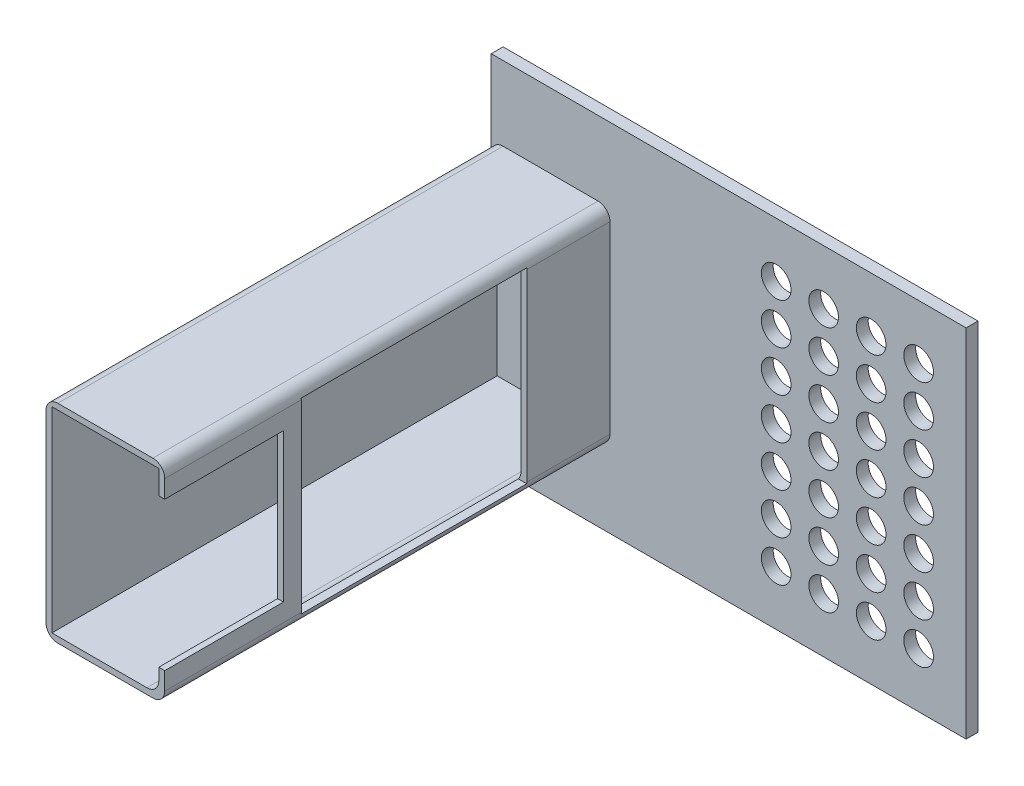
SolidWorks part; units mm, degrees
ref_plane "前视基准面" through (0, 0, 0) normal (0, 0, 1) x (1, 0, 0)
ref_plane "上视基准面" through (0, 0, 0) normal (0, 1, 0) x (1, 0, 0)
ref_plane "右视基准面" through (0, 0, 0) normal (1, 0, 0) x (0, 0, -1)
other "Configuration Table"
sketch "草图1" plane through (0, 0, 0) normal (0, 0, 1) x (1, 0, 0)
  line L1 (0, 0) -> (80, 0)
  line L2 (0, 0) -> (0, -60)
  line L3 (0, -60) -> (80, -60)
  line L4 (80, 0) -> (80, -60)
  dimension "D1" = 80
  dimension "D2" = 60
extrude "凸台-拉伸1" add sketch "草图1" along normal blind 2
sketch "草图3" plane through (0, 0, 2) normal (0, 0, 1) x (1, 0, 0)
  circle A5 centre (48, -50.7846) radius 2.5
  circle A6 centre (56, -50.7846) radius 2.5
  circle A7 centre (64, -50.7846) radius 2.5
  circle A8 centre (72, -50.7846) radius 2.5
  circle A13 centre (48, -43.8564) radius 2.5
  circle A14 centre (56, -43.8564) radius 2.5
  circle A15 centre (64, -43.8564) radius 2.5
  circle A16 centre (72, -43.8564) radius 2.5
  circle A22 centre (48, -36.9282) radius 2.5
  circle A23 centre (56, -36.9282) radius 2.5
  circle A24 centre (64, -36.9282) radius 2.5
  circle A25 centre (72, -36.9282) radius 2.5
  circle A30 centre (48, -30) radius 2.5
  circle A31 centre (56, -30) radius 2.5
  circle A32 centre (64, -30) radius 2.5
  circle A33 centre (72, -30) radius 2.5
  circle A39 centre (48, -23.0718) radius 2.5
  circle A40 centre (56, -23.0718) radius 2.5
  circle A41 centre (64, -23.0718) radius 2.5
  circle A42 centre (72, -23.0718) radius 2.5
  circle A47 centre (48, -16.1436) radius 2.5
  circle A48 centre (56, -16.1436) radius 2.5
  circle A49 centre (64, -16.1436) radius 2.5
  circle A50 centre (72, -16.1436) radius 2.5
  circle A56 centre (48, -9.2154) radius 2.5
  circle A57 centre (56, -9.2154) radius 2.5
  circle A58 centre (64, -9.2154) radius 2.5
  circle A59 centre (72, -9.2154) radius 2.5
extrude "HoneycombCooling" cut sketch "草图3" against normal through all
sketch "草图4" plane through (0, 0, 2) normal (0, 0, 1) x (1, 0, 0)
  line L0 (0, 0) -> (0, -60) construction
  line L1 (0, -12.5) -> (20, -12.5)
  line L2 (0, -12.5) -> (0, -47.5)
  line L3 (0, -47.5) -> (20, -47.5)
  line L4 (20, -12.5) -> (20, -47.5)
  line L5 (0, -60) -> (80, -60) construction
  dimension "D1" = 35
  dimension "D2" = 12.5
  dimension "D3" = 20
extrude "凸台-拉伸2" add sketch "草图4" along normal blind 75
sketch "草图5" plane through (0, 0, 77) normal (0, 0, 1) x (1, 0, 0)
  line L0 (20, -47.5) -> (20, -12.5) construction
  line L1 (1, -13.5) -> (19, -13.5)
  line L2 (1, -13.5) -> (1, -46.5)
  line L3 (1, -46.5) -> (19, -46.5)
  line L4 (19, -13.5) -> (19, -46.5)
  line L5 (20, -12.5) -> (0, -12.5) construction
  line L6 (0, -12.5) -> (0, -47.5) construction
  line L7 (0, -47.5) -> (20, -47.5) construction
  dimension "D1" = 1
  dimension "D2" = 1
  dimension "D3" = 1
  dimension "D4" = 1
extrude "切除-拉伸3" cut sketch "草图5" against normal blind 75
sketch "草图6" plane through (20, 0, 0) normal (1, 0, 0) x (0, 0, -1)
  line L0 (-77, -47.5) -> (-2, -47.5) construction
  line L1 (-54, -14.25) -> (-16, -14.25)
  line L2 (-54, -14.25) -> (-54, -45.75)
  line L3 (-54, -45.75) -> (-16, -45.75)
  line L4 (-16, -14.25) -> (-16, -45.75)
  line L5 (-2, -47.5) -> (-2, -12.5) construction
  line L7 (-77, -47.5) -> (-77, -12.5) construction
  dimension "D1" = 38
  dimension "D2" = 31.5
  dimension "D3" = 1.75
  dimension "D4" = 14
  dimension "D5" = 23
extrude "切除-拉伸4" cut sketch "草图6" against normal blind 8 contours L2 L3 L4 L1
ref_plane "基准面1" through (0, 0, 54) normal (0, 0, 1) x (1, 0, 0)
sketch "草图8" plane through (0, 0, 54) normal (0, 0, 1) x (1, 0, 0)
  line L1 (1, -13.5) -> (19, -13.5)
  line L2 (1, -13.5) -> (1, -46.5)
  line L3 (1, -46.5) -> (19, -46.5)
  line L4 (19, -13.5) -> (19, -46.5)
sketch "草图9" plane through (20, 0, 0) normal (1, 0, 0) x (0, 0, -1)
  line L0 (-77, -47.5) -> (-77, -12.5) construction
  line L1 (-77, -17.5) -> (-57, -17.5)
  line L2 (-77, -17.5) -> (-77, -42.5)
  line L3 (-77, -42.5) -> (-57, -42.5)
  line L4 (-57, -17.5) -> (-57, -42.5)
  line L5 (-77, -12.5) -> (-2, -12.5) construction
  line L6 (-77, -47.5) -> (-2, -47.5) construction
  dimension "D1" = 20
  dimension "D2" = 25
  dimension "D3" = 5
  dimension "D4" = 5
extrude "切除-拉伸5" cut sketch "草图9" against normal blind 10 contours L1 L4 L3 L2
fillet "圆角1" radius 2 4 edges at (19, -46.5, 39.5) (0, -47.5, 39.5) (0, -12.5, 39.5) (20, -12.5, 39.5)
fillet "圆角2" radius 2 1 edges at (20, -47.5, 39.5)
